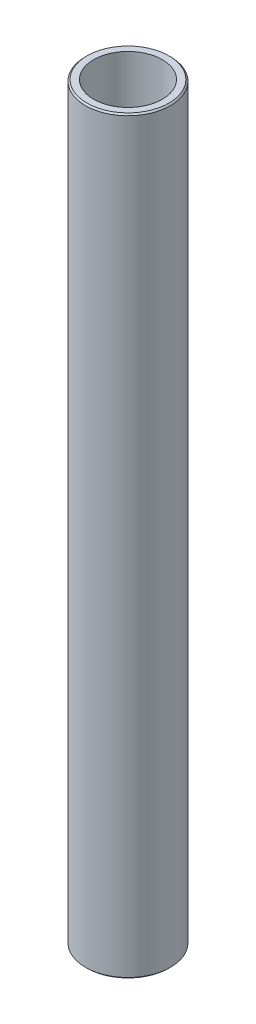
SolidWorks part; units mm, degrees
ref_plane "Front Plane" through (0, 0, 0) normal (0, 0, 1) x (1, 0, 0)
ref_plane "Top Plane" through (0, 0, 0) normal (0, 1, 0) x (1, 0, 0)
ref_plane "Right Plane" through (0, 0, 0) normal (1, 0, 0) x (0, 0, -1)
sketch "Sketch1" plane through (0, 0, 0) normal (0, 1, 0) x (1, 0, 0)
  circle A0 centre (0, 0) radius 20
  dimension "SHAFT_OD" = 40
extrude "Boss-Extrude1" add sketch "Sketch1" along normal blind 353.0673
sketch "Sketch2" plane through (0, 0, 0) normal (0, 1, 0) x (1, 0, 0)
  circle A0 centre (0, 0) radius 16.1932
  dimension "BORE_D" = 32.3865
extrude "Cut-Extrude1" cut sketch "Sketch2" along normal through all
chamfer "Chamfer1" distance 0.6906 angle 45 2 edges at (0, 353.0673, 20) (0, 0, 20)
